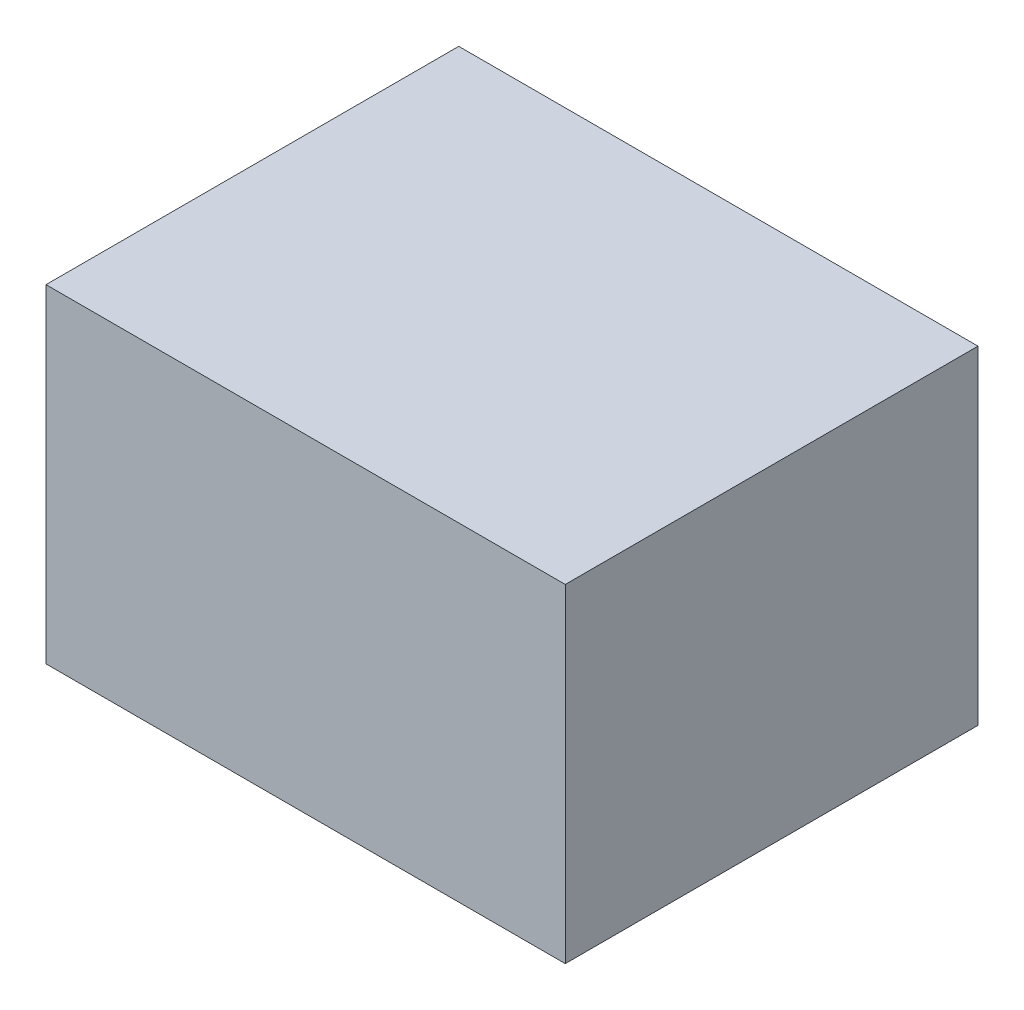
SolidWorks part; units mm, degrees
ref_plane "Front Plane" through (0, 0, 0) normal (0, 0, 1) x (1, 0, 0)
ref_plane "Top Plane" through (0, 0, 0) normal (0, 1, 0) x (1, 0, 0)
ref_plane "Right Plane" through (0, 0, 0) normal (1, 0, 0) x (0, 0, -1)
sketch "Sketch2" plane through (0, 0, 0) normal (0, 0, 1) x (1, 0, 0)
  line L1 (1471.8699, 931.722) -> (-14.0301, 931.722)
  line L2 (1471.8699, 931.722) -> (1471.8699, -8.078)
  line L3 (1471.8699, -8.078) -> (-14.0301, -8.078)
  line L4 (-14.0301, 931.722) -> (-14.0301, -8.078)
extrude "Boss-Extrude1" add sketch "Sketch2" along normal blind 1181.1 contours L1 L4 L3 L2
